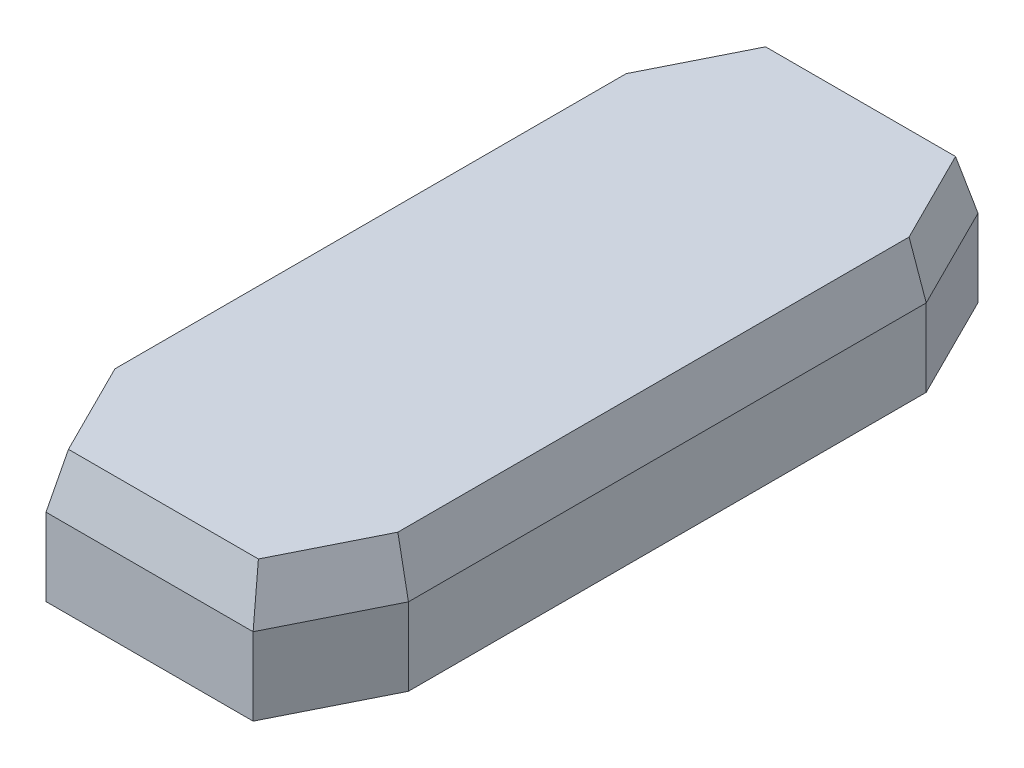
SolidWorks part; units mm, degrees
ref_plane "Front Plane" through (0, 0, 0) normal (0, 0, 1) x (1, 0, 0)
ref_plane "Top Plane" through (0, 0, 0) normal (0, 1, 0) x (1, 0, 0)
ref_plane "Right Plane" through (0, 0, 0) normal (1, 0, 0) x (0, 0, -1)
sketch "Sketch1" plane through (0, 0, 0) normal (0, 1, 0) x (1, 0, 0)
  line L0 (-7.62, 12.7) -> (-5.08, 17.78)
  line L1 (-5.08, 17.78) -> (5.08, 17.78)
  line L2 (-7.62, 12.7) -> (-7.62, -12.7)
  line L3 (-5.08, -17.78) -> (5.08, -17.78)
  line L4 (7.62, 12.7) -> (7.62, -12.7)
  line L5 (-7.62, 17.78) -> (7.62, -17.78) construction
  line L6 (-7.62, -17.78) -> (7.62, 17.78) construction
  line L7 (5.08, 17.78) -> (7.62, 12.7)
  line L8 (5.08, -17.78) -> (7.62, -12.7)
  line L9 (-7.62, -12.7) -> (-5.08, -17.78)
  point P0 (0, 0)
  dimension "D1" = 15.24
  dimension "D2" = 35.56
  dimension "D3" = 2.54
  dimension "D4" = 5.08
  dimension "D5" = 2.54
  dimension "D6" = 5.08
  dimension "D7" = 2.54
  dimension "D8" = 5.08
  dimension "D9" = 5.08
  dimension "D10" = 2.54
extrude "Boss-Extrude1" add sketch "Sketch1" along normal blind 2.54 draft 15
sketch "Stem" plane through (0, 0, 0) normal (0, -1, 0) x (1, 0, 0)
  line L1 (-0.5625, 2.075) -> (0.5625, 2.075)
  line L2 (-0.5625, 2.075) -> (-0.5625, -2.075)
  line L3 (-0.5625, -2.075) -> (0.5625, -2.075)
  line L4 (0.5625, 2.075) -> (0.5625, -2.075)
  line L5 (-0.5625, 2.075) -> (0.5625, -2.075) construction
  line L6 (-0.5625, -2.075) -> (0.5625, 2.075) construction
  line L7 (2.0625, 0.6625) -> (-2.0625, 0.6625)
  line L8 (2.0625, 0.6625) -> (2.0625, -0.6625)
  line L9 (2.0625, -0.6625) -> (-2.0625, -0.6625)
  line L10 (-2.0625, 0.6625) -> (-2.0625, -0.6625)
  line L11 (2.0625, 0.6625) -> (-2.0625, -0.6625) construction
  line L12 (2.0625, -0.6625) -> (-2.0625, 0.6625) construction
  line L13 (-2.5, 2.375) -> (2.5, 2.375)
  line L14 (-3, 1.875) -> (-3, -1.875)
  line L15 (-2.5, -2.375) -> (2.5, -2.375)
  line L16 (3, 1.875) -> (3, -1.875)
  line L17 (-3, 2.375) -> (3, -2.375) construction
  line L18 (-3, -2.375) -> (3, 2.375) construction
  arc A0 (-3, -1.875) -> (-2.5, -2.375) centre (-2.5, -1.875) ccw
  arc A1 (-2.5, 2.375) -> (-3, 1.875) centre (-2.5, 1.875) ccw
  arc A2 (2.5, -2.375) -> (3, -1.875) centre (2.5, -1.875) ccw
  arc A3 (2.5, 2.375) -> (3, 1.875) centre (2.5, 1.875) cw
  point P0 (0, 0)
  point P6 (0, 0)
  point P11 (0, 0)
  dimension "D7" = 0.5
  dimension "D1" = 4.15
  dimension "D2" = 1.125
  dimension "D3" = 1.325
  dimension "D4" = 4.125
  dimension "D5" = 4.75
  dimension "D6" = 6
extrude "Boss-Extrude2" add sketch "Stem" along normal blind 3.8 contours A3 L13 A1 L14 A0 L15 A2 L16 L10 L7 L2 L1 L4 L8 L9 L3 region at (0, 0, 2.2985)
fillet "Fillet1" radius 0.5 8 edges at (-2.8536, 0, 2.2286) (0, 0, 2.375) (2.8536, 0, 2.2286) (3, 0, 0) (2.8536, 0, -2.2286) (0, 0, -2.375) (-2.8536, 0, -2.2286) (-3, 0, 0)
fillet "Fillet2" radius 0.1 8 edges at (-2.8536, -3.8, -2.2286) (-3, -3.8, 0) (-2.8536, -3.8, 2.2286) (0, -3.8, 2.375) (2.8536, -3.8, 2.2286) (3, -3.8, 0) (2.8536, -3.8, -2.2286) (0, -3.8, -2.375)
chamfer "Chamfer1" distance 0.2 angle 45 11 edges at (-0.5625, -3.8, -1.3688) (-1.3125, -3.8, -0.6625) (-2.0625, -3.8, 0) (0.5625, -3.8, -1.3688) (1.3125, -3.8, -0.6625) (2.0625, -3.8, 0) (1.3125, -3.8, 0.6625) (0.5625, -3.8, 1.3687) (0, -3.8, 2.075) (-0.5625, -3.8, 1.3687) (-1.3125, -3.8, 0.6625)
sketch "Sketch3" plane through (0, 0, 0) normal (0, -1, 0) x (1, 0, 0)
  line L0 (-7.62, 12.7) -> (-7.62, -12.7)
  line L1 (-7.62, -12.7) -> (-5.08, -17.78)
  line L2 (-5.08, -17.78) -> (5.08, -17.78)
  line L3 (5.08, -17.78) -> (7.62, -12.7)
  line L4 (7.62, -12.7) -> (7.62, 12.7)
  line L5 (7.62, 12.7) -> (5.08, 17.78)
  line L6 (5.08, 17.78) -> (-5.08, 17.78)
  line L7 (-5.08, 17.78) -> (-7.62, 12.7)
  line L44 (-6.35, -12.4002) -> (-4.2951, -16.51)
  line L45 (-4.2951, -16.51) -> (4.2951, -16.51)
  line L46 (4.2951, -16.51) -> (6.35, -12.4002)
  line L47 (6.35, -12.4002) -> (6.35, 12.4002)
  line L48 (6.35, 12.4002) -> (4.2951, 16.51)
  line L49 (4.2951, 16.51) -> (-4.2951, 16.51)
  line L50 (-4.2951, 16.51) -> (-6.35, 12.4002)
  line L51 (-6.35, 12.4002) -> (-6.35, -12.4002)
  line L52 (-6.35, -12.4002) -> (-4.2951, -16.51)
  line L53 (-4.2951, -16.51) -> (4.2951, -16.51)
  line L54 (4.2951, -16.51) -> (6.35, -12.4002)
  line L55 (6.35, -12.4002) -> (6.35, 12.4002)
  line L56 (6.35, 12.4002) -> (4.2951, 16.51)
  line L57 (4.2951, 16.51) -> (-4.2951, 16.51)
  line L58 (-4.2951, 16.51) -> (-6.35, 12.4002)
  line L59 (-6.35, 12.4002) -> (-6.35, -12.4002)
  dimension "D1" = 1.27
extrude "Boss-Extrude3" add sketch "Sketch3" along normal blind 3.8
